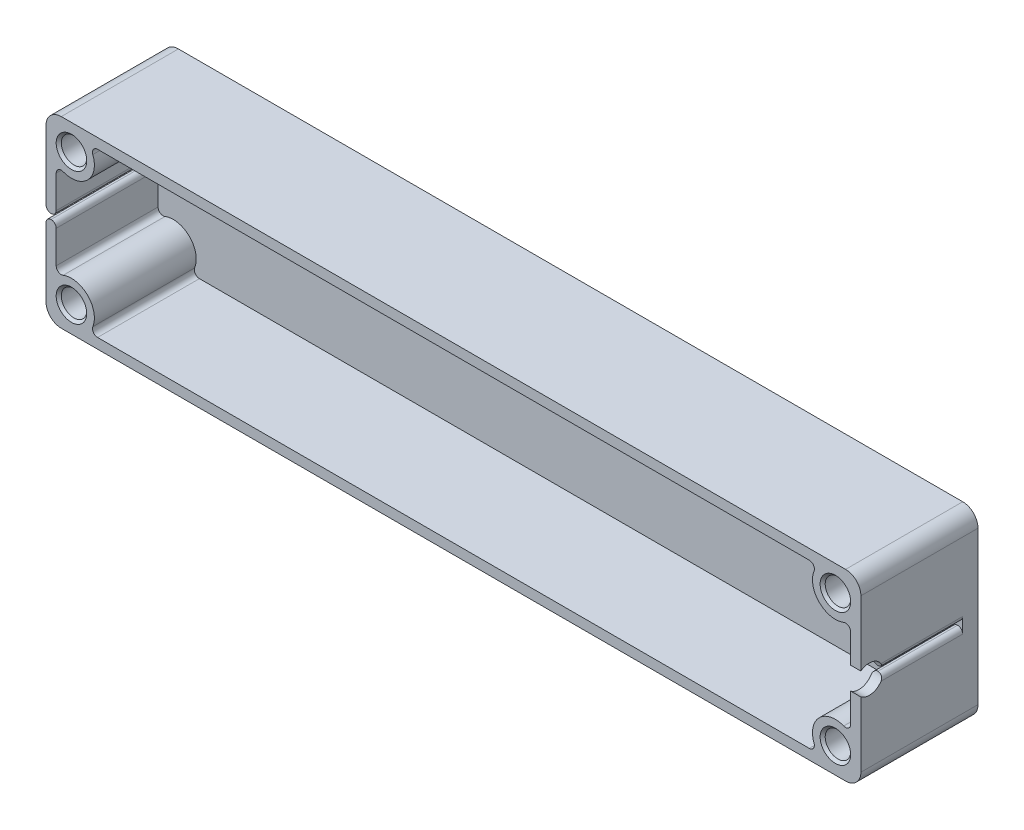
SolidWorks part; units mm, degrees
ref_plane "Front" through (0, 0, 0) normal (0, 0, 1) x (1, 0, 0)
ref_plane "Top" through (0, 0, 0) normal (0, 1, 0) x (1, 0, 0)
ref_plane "Right" through (0, 0, 0) normal (1, 0, 0) x (0, 0, -1)
sketch "Sketch1" plane through (0, 0, 0) normal (0, 0, 1) x (1, 0, 0)
  line L1 (-80, 18) -> (80, 18)
  line L2 (-80, 18) -> (-80, -18)
  line L3 (-80, -18) -> (80, -18)
  line L4 (80, 18) -> (80, -18)
  point P4 (0, 18)
  point P6 (-80, 0)
  dimension "D1" = 160
  dimension "D2" = 36
extrude "Boss-Extrude1" add sketch "Sketch1" along normal blind 3
sketch "Sketch3" plane through (0, 0, 3) normal (0, 0, 1) x (1, 0, 0)
  line L0 (78, 16) -> (-78, 16)
  line L1 (-78, 16) -> (-78, -16)
  line L2 (-78, -16) -> (78, -16)
  line L3 (78, -16) -> (78, 16)
  line L4 (-80, 18) -> (-80, -18)
  line L5 (-80, -18) -> (80, -18)
  line L6 (80, -18) -> (80, 18)
  line L7 (80, 18) -> (-80, 18)
  line L8 (-80, 18) -> (-80, -18)
  line L9 (-80, -18) -> (80, -18)
  line L10 (80, -18) -> (80, 18)
  line L11 (80, 18) -> (-80, 18)
  dimension "D1" = 0
  dimension "D2" = 2
extrude "Boss-Extrude3" add sketch "Sketch3" along normal blind 20
sketch "Sketch4" plane through (0, 0, 23) normal (0, 0, 1) x (1, 0, 0)
  line L0 (78, -16) -> (78, 16) construction
  line L1 (78, 0.5) -> (80, 0.5)
  line L2 (78, 0.5) -> (78, -0.5)
  line L3 (78, -0.5) -> (80, -0.5)
  line L4 (80, 0.5) -> (80, -0.5)
  line L5 (80, -18) -> (80, 18) construction
  point P8 (78, 0)
  dimension "D1" = 1
extrude "Cut-Extrude1" cut sketch "Sketch4" against normal up to surface (20 mm away) up to face at (0, 0, 3)
sketch "Sketch5" plane through (0, 0, 3) normal (0, 0, 1) x (1, 0, 0)
  line L0 (80, 0.5) -> (80, 18) construction
  line L1 (80, 18) -> (-80, 18) construction
  line L2 (-80, -18) -> (80, -18) construction
  circle A2 centre (75, 13) radius 4.5
  circle A3 centre (75, -13) radius 4.5
  point P4 (0, 0)
  dimension "D4" = 9
  dimension "D1" = 5
  dimension "D2" = 5
  dimension "D3" = 5
extrude "Boss-Extrude4" add sketch "Sketch5" along normal up to surface (20 mm away) up to face at (26.3333, 0, 23)
hole_wizard "Ø5.0mm Dowel Hole1" positions "Sketch6" profile "Sketch7" hole size "Ø5.0" standard "ANSI Metric"
sketch "Sketch6" plane through (0, 0, 23) normal (0, 0, 1) x (1, 0, 0)
  point P0 (75, 13)
  point P3 (75, -13)
sketch "Sketch7" plane through (75, 13, 23) normal (1, 0, 0) x (0, -1, 0)
  line L0 (0, 0) -> (0, 4.6)
  line L1 (0, 4.6) -> (2.5, 4.6)
  line L2 (2.5, 4.6) -> (2.5, 0.5)
  line L3 (2.5, 0.5) -> (3, 0)
  line L5 (3, 0) -> (0, 0)
  line L6 (-2.5, 0.5) -> (-3, 0) construction
  line L10 (0, 4.6) -> (-2.5, 4.6) construction
  line L11 (0, -6.35) -> (0, 107.95) construction
  dimension "Hole Dia." = 5
  dimension "Hole Depth" = 4.6
  dimension "Near C'Sink Dia." = 6
  dimension "Near C'Sink Angle" = 90
  dimension "Drill Angle" = 180
fillet "Fillet3" radius 3 4 edges at (-80, 18, 11.5) (80, 18, 11.5) (-80, -18, 11.5) (80, -18, 11.5)
hole_wizard "M5 Clearance Hole2" positions "Sketch11" profile "Sketch12" hole size "M5" standard "ANSI Metric" end condition through all
sketch "Sketch11" plane through (0, 0, 0) normal (0, 0, -1) x (-1, 0, 0)
  line L0 (-80, -15) -> (-80, 15) construction
  line L1 (80, 15) -> (80, -15) construction
  point P0 (-70, 0)
  point P2 (70, 0)
  dimension "D1" = 10
  dimension "D2" = 10
sketch "Sketch12" plane through (70, 0, 0) normal (1, 0, 0) x (0, 1, 0)
  line L0 (0, 0) -> (0, 23)
  line L1 (0, 23) -> (2.75, 23)
  line L2 (2.75, 23) -> (2.75, 0)
  line L5 (2.75, 0) -> (0, 0)
  line L11 (0, -6.35) -> (0, 107.95) construction
  dimension "Thru Hole Dia." = 5.5
  dimension "Thru Hole Depth" = 23
mirror "Mirror2" about plane through (0, 0, 0) normal (1, 0, 0) of "Boss-Extrude4", "Ø5.0mm Dowel Hole1", "M5 Clearance Hole2", "Cut-Extrude1"
fillet "Fillet4" radius 1 16 edges at (-78, -9.6459, 13) (-78, -0.5, 13) (-80, -0.5, 13) (-80, 0.5, 13) (-78, 0.5, 13) (-78, 9.6459, 13) (-71.6459, 16, 13) (71.6459, 16, 13) (78, 0.5, 13) (80, 0.5, 13) (80, -0.5, 13) (78, -0.5, 13) (78, -9.6459, 13) (71.6459, -16, 13) (-71.6459, -16, 13) (78, 9.6459, 13)
hole_wizard "M5 Clearance Hole3" positions "Sketch13" profile "Sketch14" hole size "M5" standard "ANSI Metric"
sketch "Sketch13" plane through (80, 0, 0) normal (1, 0, 0) x (0, 0, -1)
  point P0 (-21.3514, 0)
  point P5 (0, 0)
  point P7 (0, 0)
  point P8 (-21.3514, 0)
sketch "Sketch14" plane through (80, 0, 21.3514) normal (0, 1, 0) x (0, 0, -1)
  line L0 (0, 0) -> (0, 11.6524)
  line L1 (0, 11.6524) -> (2.75, 10)
  line L2 (2.75, 10) -> (2.75, 0)
  line L5 (2.75, 0) -> (0, 0)
  line L10 (0, 11.6524) -> (-2.75, 10) construction
  line L11 (0, -6.35) -> (0, 107.95) construction
  dimension "Hole Dia." = 5.5
  dimension "Hole Depth" = 10
  dimension "Drill Angle" = 118
